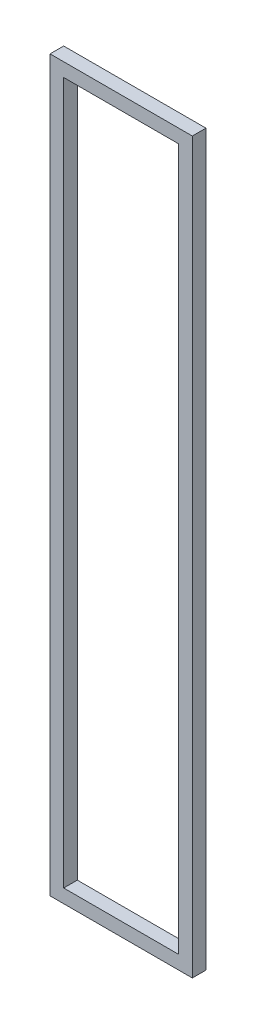
SolidWorks part; units mm, degrees
ref_plane "Front Plane" through (0, 0, 0) normal (0, 0, 1) x (1, 0, 0)
ref_plane "Top Plane" through (0, 0, 0) normal (0, 1, 0) x (1, 0, 0)
ref_plane "Right Plane" through (0, 0, 0) normal (1, 0, 0) x (0, 0, -1)
sketch "Sketch1" plane through (0, 0, 0) normal (0, 0, 1) x (1, 0, 0)
  line L1 (-38.2903, 1324.4714) -> (226.8349, 1324.4714)
  line L2 (-38.2903, 1324.4714) -> (-38.2903, -34.4286)
  line L3 (-38.2903, -34.4286) -> (226.8349, -34.4286)
  line L4 (226.8349, 1324.4714) -> (226.8349, -34.4286)
  line L5 (-12.8903, 1299.0714) -> (201.4349, 1299.0714)
  line L6 (-12.8903, 1299.0714) -> (-12.8903, -9.0286)
  line L7 (-12.8903, -9.0286) -> (201.4349, -9.0286)
  line L8 (201.4349, 1299.0714) -> (201.4349, -9.0286)
  dimension "D1" = 25.4
  dimension "D2" = 25.4
  dimension "D3" = 25.4
  dimension "D4" = 25.4
  dimension "D5" = 265.1252
  dimension "D6" = 1358.9
extrude "Extrude1" add sketch "Sketch1" along normal blind 25.4
sketch "Sketch2" plane through (0, 1324.4714, 0) normal (0, 1, 0) x (1, 0, 0)
  line L1 (226.8349, -25.4) -> (226.8349, 0) construction
  point P0 (227.6223, 0)
  dimension "D1" = 0.7874
ref_axis "Hinge Axis 1" through (227.6223, 1324.4714, 0) along (0, 1, 0)
sketch "Sketch3" plane through (0, 1324.4714, 0) normal (0, 1, 0) x (1, 0, 0)
  line L0 (-38.2903, -25.4) -> (-38.2903, 0) construction
  point P0 (-39.0777, -25.4)
  dimension "D1" = 0.7874
ref_axis "Hinge axis 2" through (-39.0777, 1324.4714, 25.4) along (0, 1, 0)
